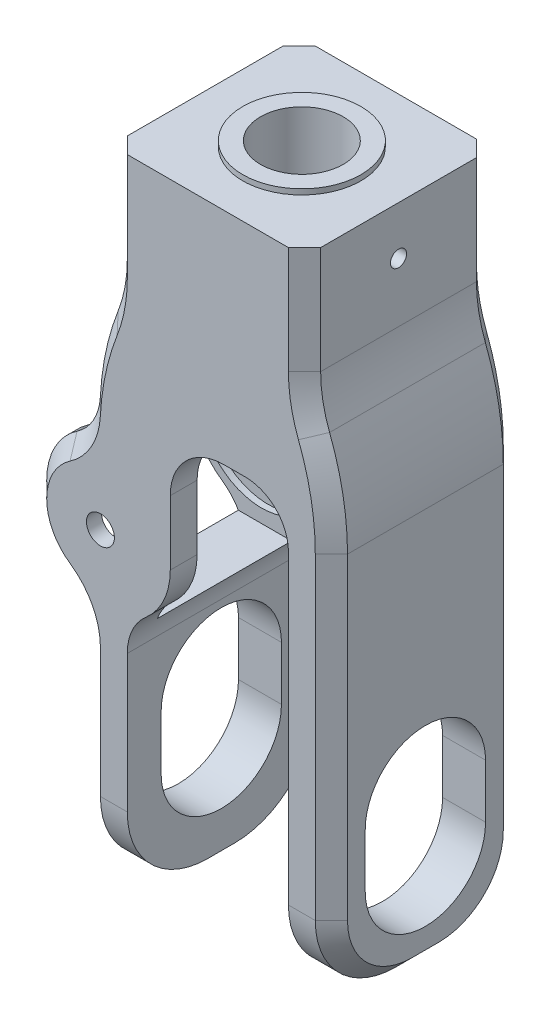
SolidWorks part; units mm, degrees
note: '?' marks a value the reader was unsure of.
ref_plane "Front Plane" through (0, 0, 0) normal (0, 0, 1) x (1, 0, 0)
ref_plane "Top Plane" through (0, 0, 0) normal (0, 1, 0) x (1, 0, 0)
ref_plane "Right Plane" through (0, 0, 0) normal (1, 0, 0) x (0, 0, -1)
sketch "Sketch1" plane through (0, 0, 0) normal (0, 1, 0) x (1, 0, 0)
  line L1 (-23, -17.5) -> (23, -17.5)
  line L2 (-23, -17.5) -> (-23, 17.5)
  line L3 (-23, 17.5) -> (23, 17.5)
  line L4 (23, -17.5) -> (23, 17.5)
  line L5 (-23, -17.5) -> (23, 17.5) construction
  line L6 (-23, 17.5) -> (23, -17.5) construction
  circle A0 centre (0, 0) radius 7.7
  point P0 (0, 0)
  dimension "D3" = 15.4
  dimension "D1" = 46
  dimension "D2" = 35
extrude "Boss-Extrude1" add sketch "Sketch1" along normal blind 36
sketch "Sketch2" plane through (0, 36, 0) normal (0, 1, 0) x (1, 0, 0)
  circle A0 centre (0, 0) radius 11
  circle A1 centre (0, 0) radius 7.7
  dimension "D1" = 22
extrude "Boss-Extrude2" add sketch "Sketch2" along normal blind 1
sketch "Sketch3" plane through (0, 0, 0) normal (0, -1, 0) x (1, 0, 0)
  line L0 (23, -17.5) -> (-23, -17.5) construction
  line L1 (-23, 17.5) -> (-15, 17.5)
  line L2 (-23, 17.5) -> (-23, -17.5)
  line L3 (-23, -17.5) -> (-15, -17.5)
  line L4 (-15, 17.5) -> (-15, -17.5)
  dimension "D1" = 8
extrude "Boss-Extrude3" add sketch "Sketch3" along normal blind 85
sketch "Sketch4" plane through (0, 0, 0) normal (0, -1, 0) x (1, 0, 0)
  line L1 (23, 17.5) -> (-15, 17.5)
  line L2 (23, 17.5) -> (23, -17.5)
  line L3 (23, -17.5) -> (-15, -17.5)
  line L4 (-15, 17.5) -> (-15, -17.5)
  circle A0 centre (0, 0) radius 8.2
  dimension "D1" = 16.4
extrude "Boss-Extrude4" add sketch "Sketch4" along normal blind 5
sketch "Sketch5" plane through (0, 0, 17.5) normal (0, 0, 1) x (1, 0, 0)
  line L2 (23, -5) -> (-15, -5) construction
  circle A0 centre (-20, -27) radius 2.6
  dimension "D1" = 22
  dimension "D2" = 20
  dimension "D3" = 5.2
extrude "Cut-Extrude1" cut sketch "Sketch5" against normal blind 66
sketch "Sketch6" plane through (0, 0, 17.5) normal (0, 0, 1) x (1, 0, 0)
  line L0 (-7, -27) -> (-7, -5)
  line L1 (23, -5) -> (-15, -5) construction
  line L2 (-7, -5) -> (-15, -5)
  line L3 (-15, -5) -> (-15, -39)
  line L5 (-23, -14.3509) -> (-23, -39.6491)
  arc A0 (-23, -14.3509) -> (-23, -39.6491) centre (-20, -27) ccw
  arc A1 (-15, -39) -> (-7, -27) centre (-20, -27) ccw
  dimension "D1" = 26
extrude "Boss-Extrude5" add sketch "Sketch6" against normal up to surface (35 mm away) up to face at (-17.4, -27, -17.5)
sketch "Sketch7" plane through (0, -5, 0) normal (0, -1, 0) x (1, 0, 0)
  line L0 (-7, -17.5) -> (23, -17.5) construction
  line L1 (23, 17.5) -> (15, 17.5)
  line L2 (23, 17.5) -> (23, -17.5)
  line L3 (23, -17.5) -> (15, -17.5)
  line L4 (15, 17.5) -> (15, -17.5)
  dimension "D1" = 8
extrude "Boss-Extrude6" add sketch "Sketch7" along normal up to surface (80 mm away) up to face at (-19, -85, 0)
fillet "Fillet1" radius 15 4 edges at (-19, -85, -17.5) (19, -85, -17.5) (19, -85, 17.5) (-19, -85, 17.5)
fillet "Fillet2" radius 10 2 edges at (-23, -14.3509, 0) (-15, -39, 0)
fillet "Fillet3" radius 8 1 edges at (15, -5, 0)
sketch "Sketch8" plane through (0, 0, 17.5) normal (0, 0, 1) x (1, 0, 0)
  line L0 (-18, 36) -> (-18, 16)
  line L1 (-18, 36) -> (-23, 36)
  line L2 (-23, 36) -> (-23, 1)
  line L3 (18, 16) -> (18, 36)
  line L4 (18, 36) -> (23, 36)
  line L5 (23, 36) -> (23, 1)
  line L6 (-23, 36) -> (23, 36) construction
  line L8 (-23, 36) -> (-23, -8.0263) construction
  arc A0 (-18, 16) -> (-23, 1) centre (-43, 16) cw
  arc A1 (23, 1) -> (18, 16) centre (43, 16) cw
  dimension "D2" = 25
  dimension "D1" = 5
  dimension "D3" = 35
  dimension "D4" = 5
extrude "Cut-Extrude2" cut sketch "Sketch8" against normal blind 66
fillet "Fillet4" radius 50 2 edges at (-23, 1, 0) (23, 1, 0)
sketch "Sketch9" plane through (0, 0, 0) normal (0, 0, 1) x (1, 0, 0)
  line L0 (-7, -5) -> (-7, -41)
  line L1 (-33, -41) -> (-7, -41) construction
  line L2 (-33, -41) -> (-33, -13) construction
  line L3 (-33, -13) -> (-7, -13) construction
  line L4 (-7, -41) -> (-7, -13) construction
  line L5 (-33, -41) -> (-7, -13) construction
  line L6 (-33, -13) -> (-7, -41) construction
  line L7 (-7, -41) -> (-33, -41)
  line L8 (-33, -41) -> (-33, -5)
  line L9 (-33, -5) -> (-7, -5)
  point P0 (-20, -27)
extrude "Cut-Extrude3" cut sketch "Sketch9" against normal blind 12.5 and the other way blind 12.5
fillet "Fillet5" radius 10 2 edges at (-7, -5, 15) (-7, -5, -15)
ref_axis "Axis1" through (-20, -27, 12.5) along (0, 0, 1)?
sketch "Sketch10" plane through (-23, 0, 0) normal (-1, 0, 0) x (0, 0, 1)
  line L0 (12.5, -27) -> (17.5, -27) construction
  circle A0 centre (0, -62) radius 2.5 construction
  dimension "D2" = 5
  dimension "D1" = 35
sketch "Sketch11" plane through (-23, 0, 0) normal (-1, 0, 0) x (0, 0, 1)
  line L0 (0, -67) -> (0, -57) construction
  line L1 (-11.2, -67) -> (-11.2, -57)
  line L2 (11.2, -67) -> (11.2, -57)
  arc A0 (-11.2, -67) -> (11.2, -67) centre (0, -67) ccw
  arc A1 (11.2, -57) -> (-11.2, -57) centre (0, -57) ccw
  point P2 (0, -62)
  point P9 (-11.2, -62)
  dimension "D2" = 22.4
  dimension "D1" = 10
extrude "Cut-Extrude4" cut sketch "Sketch11" against normal through all
chamfer "Chamfer1" distance 3 angle 45 28 edges at (-18, 26, -17.5) (-18.427, 11.399, -17.5) (-21.9716, -0.6622, -17.5) (-24.2773, -12.9165, -17.5) (-33, -27, 17.5) (-33, -27, -17.5) (-24.1535, -41.3111, -17.5) (-23, -57.9868, -17.5) (-23, -80.6066, -13.1066) (-23, -85, 0) (-23, -80.6066, 13.1066) (-18, 26, 17.5) (-18.427, 11.399, 17.5) (-21.9716, -0.6622, 17.5) (-24.2773, -12.9165, 17.5) (-24.1535, -41.3111, 17.5) (-23, -57.9868, 17.5) (18, 26, -17.5) (18.4202, 11.4356, -17.5) (22.1596, -1.7971, -17.5) (23, -40.4629, -17.5) (23, -80.6066, -13.1066) (23, -85, 0) (23, -80.6066, 13.1066) (18, 26, 17.5) (18.4202, 11.4356, 17.5) (22.1596, -1.7971, 17.5) (23, -40.4629, 17.5)
sketch "Sketch12" plane through (18, 0, 0) normal (1, 0, 0) x (0, 0, -1)
  line L0 (7.7, 37) -> (-7.7, 37) construction
  circle A0 centre (0, 27) radius 1.5
  dimension "D1" = 3
  dimension "D2" = 10
extrude "Cut-Extrude5" cut sketch "Sketch12" against normal up to surface (10.3 mm away)
sketch "Sketch13" plane through (-16.25, 0, 16.25) normal (-0.7071, 0, 0.7071) x (0.7071, 0, 0.7071)
  line L0 (-2.4749, 36) -> (1.7678, 36) construction
  circle A0 centre (-0.5597, 33) radius 1.5
  dimension "D1" = 3
  dimension "D2" = 3
extrude "Cut-Extrude6" cut sketch "Sketch13" against normal up to surface (15.3386 mm away)
sketch "Sketch15" plane through (0, 0, 12.5) normal (0, 0, -1) x (-1, 0, 0)
  circle A0 centre (20, -27) radius 5
  dimension "D1" = 10
extrude "Cut-Extrude7" cut sketch "Sketch15" against normal blind 2.2
sketch "Sketch16" plane through (0, 0, -12.5) normal (0, 0, 1) x (1, 0, 0)
  circle A0 centre (-20, -27) radius 5
  dimension "D1" = 10
extrude "Cut-Extrude8" cut sketch "Sketch16" against normal blind 2.2
sketch "Sketch17" plane through (0, 0, -12.5) normal (0, 0, 1) x (1, 0, 0)
  circle A0 centre (-20, -27) radius 11.5
  dimension "D1" = 23
extrude "Cut-Extrude9" cut sketch "Sketch17" against normal blind 1.2
sketch "Sketch18" plane through (0, 0, 12.5) normal (0, 0, -1) x (-1, 0, 0)
  circle A0 centre (20, -27) radius 11.5
  dimension "D1" = 23
extrude "Cut-Extrude10" cut sketch "Sketch18" against normal blind 1.2
ref_plane "Plane1" through (0, -66.1, 0) normal (0, 1, 0) x (1, 0, 0)
sketch "Sketch19" plane through (0, -66.1, 0) normal (0, 1, 0) x (1, 0, 0)
  point P0 (0, 0)
